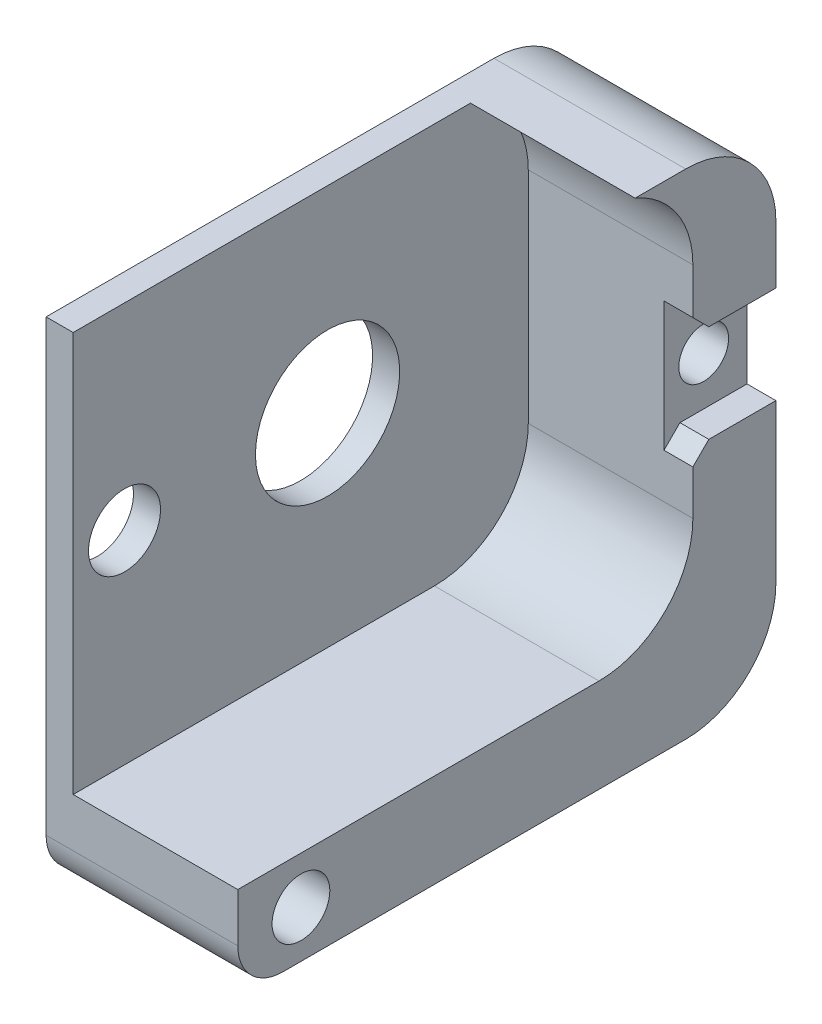
SolidWorks part; units mm, degrees
note: The reader was unsure of these and kept them because the rebuilt part matched: shared geometry of "Sketch1<3>", "Sketch1<4>".
ref_plane "Front Plane" through (0, 0, 0) normal (0, 0, 1) x (1, 0, 0)
ref_plane "Top Plane" through (0, 0, 0) normal (0, 1, 0) x (1, 0, 0)
ref_plane "Right Plane" through (0, 0, 0) normal (1, 0, 0) x (0, 0, -1)
sketch "Sketch1" plane through (-18.4867, 0, 0) normal (-1, 0, 0) x (0, 0, 1)
  line L0 (-9.6703, -7.9081) -> (-12.4703, -7.9081) construction
  line L1 (-17.4703, -12.9081) -> (-17.4703, -16.1231) construction
  line L2 (-17.4703, -16.1231) -> (-13.7532, -16.1231) construction
  line L3 (-13.7532, -16.1231) -> (-12.8703, -15.2403) construction
  line L4 (-12.8703, -15.2403) -> (-12.8703, -12.7081) construction
  line L5 (-12.8703, -24.876) -> (-12.8703, -22.406) construction
  line L6 (-12.8703, -22.406) -> (-13.7532, -21.5231) construction
  line L7 (-13.7532, -21.5231) -> (-17.4703, -21.5231) construction
  line L8 (-17.4703, -21.5231) -> (-17.4703, -30.276) construction
  line L9 (-12.4703, -35.276) -> (9.8447, -35.276) construction
  line L10 (12.3447, -32.776) -> (12.3447, -30.076) construction
  line L11 (12.3447, -30.076) -> (-7.6703, -30.076) construction
  line L12 (-12.4703, -7.9081) -> (12.3447, -7.9081) construction
  line L13 (12.3447, -7.9081) -> (12.3447, -32.776) construction
  line L14 (-12.8703, -24.876) -> (-12.8703, -12.7081) construction
  line L15 (-17.4703, -30.276) -> (-17.4703, -12.9081) construction
  line L16 (-9.6703, -7.9081) -> (-12.4703, -7.9081)
  line L17 (-17.4703, -12.9081) -> (-17.4703, -16.1231)
  line L18 (-17.4703, -16.1231) -> (-13.7532, -16.1231)
  line L19 (-13.7532, -16.1231) -> (-12.8703, -15.2403)
  line L20 (-12.8703, -15.2403) -> (-12.8703, -12.7081)
  line L21 (-12.8703, -24.876) -> (-12.8703, -22.406)
  line L22 (-12.8703, -22.406) -> (-13.7532, -21.5231)
  line L23 (-13.7532, -21.5231) -> (-17.4703, -21.5231)
  line L24 (-17.4703, -21.5231) -> (-17.4703, -30.276)
  line L25 (-12.4703, -35.276) -> (9.8447, -35.276)
  line L26 (12.3447, -32.776) -> (12.3447, -30.076)
  line L27 (12.3447, -30.076) -> (-7.6703, -30.076)
  line L28 (-12.4703, -7.9081) -> (12.3447, -7.9081)
  line L29 (12.3447, -7.9081) -> (12.3447, -32.776)
  line L30 (-12.8703, -24.876) -> (-12.8703, -12.7081)
  line L31 (-17.4703, -30.276) -> (-17.4703, -12.9081)
  arc A0 (-12.4703, -7.9081) -> (-17.4703, -12.9081) centre (-12.4703, -12.9081) ccw construction
  arc A1 (-9.6703, -7.9081) -> (-12.8703, -12.7081) centre (-7.6703, -12.7081) ccw construction
  arc A2 (-17.4703, -30.276) -> (-12.4703, -35.276) centre (-12.4703, -30.276) ccw construction
  arc A3 (9.8447, -35.276) -> (12.3447, -32.776) centre (9.8447, -32.776) ccw construction
  arc A4 (-12.8703, -24.876) -> (-7.6703, -30.076) centre (-7.6703, -24.876) ccw construction
  arc A5 (-12.4703, -7.9081) -> (-17.4703, -12.9081) centre (-12.4703, -12.9081) ccw
  arc A6 (-9.6703, -7.9081) -> (-12.8703, -12.7081) centre (-7.6703, -12.7081) ccw
  arc A7 (-17.4703, -30.276) -> (-12.4703, -35.276) centre (-12.4703, -30.276) ccw
  arc A8 (9.8447, -35.276) -> (12.3447, -32.776) centre (9.8447, -32.776) ccw
  arc A9 (-12.8703, -24.876) -> (-7.6703, -30.076) centre (-7.6703, -24.876) ccw
  circle A10 centre (9.4997, -18.8231) radius 1.995 construction
  circle A11 centre (-1.7503, -18.8231) radius 3.995 construction
  circle A12 centre (9.4997, -18.8231) radius 1.995
  circle A13 centre (-1.7503, -18.8231) radius 3.995
  circle A14 centre (8.8447, -32.676) radius 1.6 construction
  circle A15 centre (8.8447, -32.676) radius 1.6
  circle A16 centre (-15.0703, -18.8231) radius 1.38 construction
  circle A17 centre (-15.0703, -18.8231) radius 1.38
  arc M1 (-12.1703, -24.876) -> (-7.6703, -29.376) centre (-7.6703, -24.876) ccw
  line M2 (-7.6703, -29.376) -> (24.3297, -29.376)
  line M8 (24.3297, -8.2081) -> (-7.6703, -8.2081)
  arc M9 (-7.6703, -8.2081) -> (-12.1703, -12.7081) centre (-7.6703, -12.7081) ccw
  line M10 (-12.1703, -12.7081) -> (-12.1703, -24.876)
extrude "Boss-Extrude1" add sketch "Sketch1" against normal offset from surface (7.52 mm away) 0.2 from offset 0.2 contours A6 L16 A5 L17 L18 L19 L20 | A9 L21 L22 L23 L24 A7 L25 A8 L26 L27 | L31 L23 L22 L30 L19 L18
extrude "Boss-Extrude2" add sketch "Sketch1<3>" along normal up to surface (1.6 mm away) from surface contours A9 L21 L22 L23 L24 A7 L25 A8 L26 L27 | A6 L16 A5 L17 L18 L19 L20
sketch "Sketch1<3>" plane through (-18.4867, 0, 0) normal (-1, 0, 0) x (0, 0, 1) same geometry as "Sketch1"
extrude "Boss-Extrude3" add sketch "Sketch1<4>" along normal blind 1.5 from surface at 0.2 contours A9 L21 L22 L23 L24 A7 L25 A8 L26 L27 A15 | A6 L16 A5 L17 L18 L19 L20 | L31 L23 L22 L30 L19 L18 A17 | L29 A13 A12 M8 M9 M10 M1 M2 | L21 A9 L27 L29 L28 A6 L20 L30 M2 M1 M10 M9 M8 starting at face at (-18.6867, -23.7432, -6.526)
sketch "Sketch1<4>" plane through (-18.4867, 0, 0) normal (-1, 0, 0) x (0, 0, 1) same geometry as "Sketch1"
